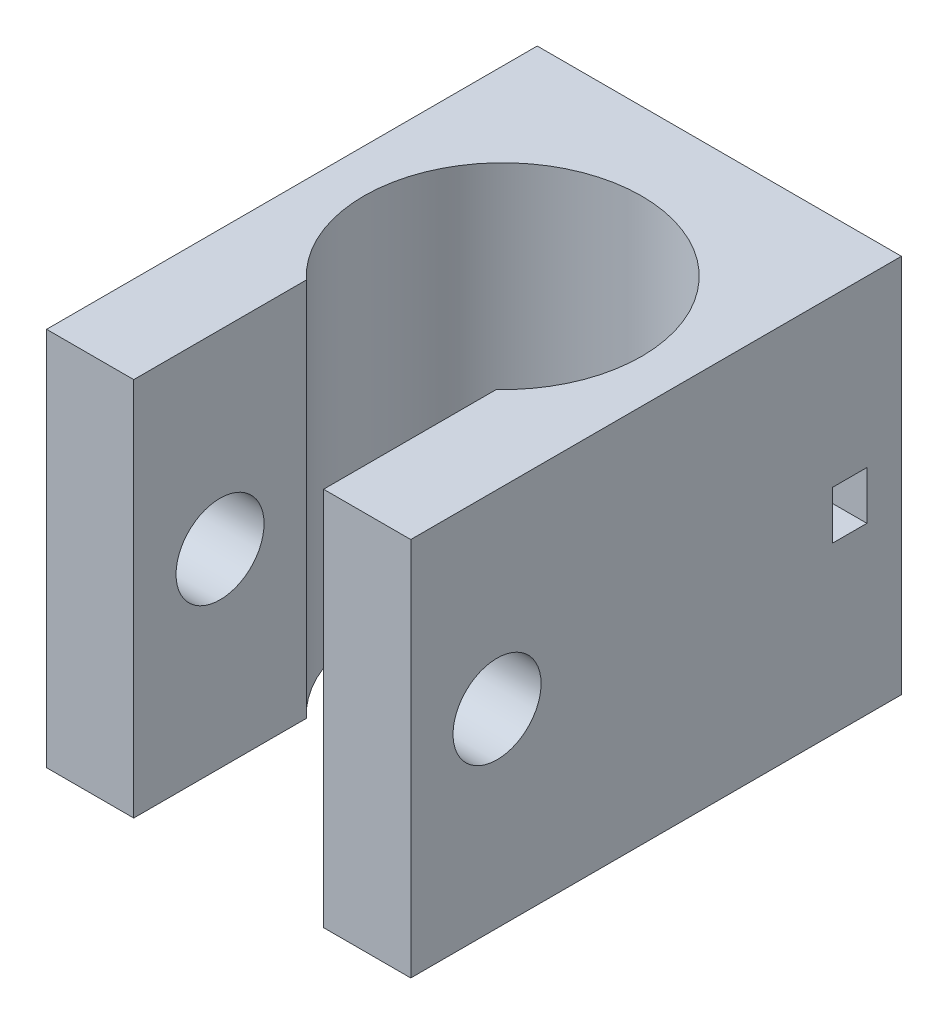
SolidWorks part; units mm, degrees
ref_plane "Front Plane" through (0, 0, 0) normal (0, 0, 1) x (1, 0, 0)
ref_plane "Top Plane" through (0, 0, 0) normal (0, 1, 0) x (1, 0, 0)
ref_plane "Right Plane" through (0, 0, 0) normal (1, 0, 0) x (0, 0, -1)
sketch "Sketch1" plane through (0, 0, 0) normal (0, 1, 0) x (1, 0, 0)
  line L0 (-5.5, -15) -> (-10.55, -15)
  line L1 (-10.55, -15) -> (-10.55, 13.4281)
  line L2 (-10.55, 13.4281) -> (10.55, 13.4281)
  line L3 (10.55, 13.4281) -> (10.55, -15)
  line L4 (10.55, -15) -> (5.5, -15)
  line L5 (5.5, -15) -> (5.5, -5)
  line L6 (-5.5, -15) -> (-5.5, -5)
  line L7 (-44.2539, 0) -> (44.2539, 0) construction
  line L8 (0, -44.7868) -> (0, 44.7868) construction
  arc A0 (-5.5, -5) -> (5.5, -5) centre (0, 0.8781) cw
  dimension "D1" = 8.05
  dimension "D2" = 11
  dimension "D3" = 10
  dimension "D4" = 10
  dimension "D5" = 21.1
  dimension "D6" = 12.55
  dimension "D7" = 15
  dimension "D8" = 10.55
extrude "Boss-Extrude1" add sketch "Sketch1" along normal mid plane 22
sketch "Sketch2" plane through (10.55, 0, 0) normal (1, 0, 0) x (0, 0, -1)
  line L0 (55, 0) -> (-55, 0) construction
  line L1 (-15, 11) -> (-15, -11) construction
  circle A0 centre (-10, 0) radius 2.55
  dimension "D1" = 5
  dimension "D2" = 5.1
extrude "Cut-Extrude1" cut sketch "Sketch2" against normal up to surface (21.1 mm away) up to face at (-10.55, 0, 0.7859)
sketch "Sketch4" plane through (10.55, 0, 0) normal (1, 0, 0) x (0, 0, -1)
  line L1 (9.4281, 1.4) -> (11.4281, 1.4)
  line L2 (9.4281, 1.4) -> (9.4281, -1.4)
  line L3 (9.4281, -1.4) -> (11.4281, -1.4)
  line L4 (11.4281, 1.4) -> (11.4281, -1.4)
  line L5 (-15, 11) -> (13.4281, 11) construction
  line L7 (13.4281, 11) -> (13.4281, -11) construction
  point P6 (10.4281, 1.4)
  dimension "D1" = 2
  dimension "D2" = 2.8
  dimension "D3" = 9.6
  dimension "D4" = 2
extrude "Cut-Extrude3" cut sketch "Sketch4" against normal up to surface (21.1 mm away) up to face at (-10.55, 0, 7.45)
sketch "Sketch5" plane through (0, 0, -13.4281) normal (0, 0, -1) x (-1, 0, 0)
  line L0 (10.55, 11) -> (10.55, -11) construction
  line L1 (-2.4, 8.55) -> (2.5, 8.55)
  line L2 (-2.4, 8.55) -> (-2.4, 3.65)
  line L3 (-2.4, 3.65) -> (2.5, 3.65)
  line L4 (2.5, 8.55) -> (2.5, 3.65)
  line L5 (2.5, -3.65) -> (-2.4, -3.65)
  line L6 (2.5, -3.65) -> (2.5, -8.55)
  line L7 (2.5, -8.55) -> (-2.4, -8.55)
  line L8 (-2.4, -3.65) -> (-2.4, -8.55)
  line L10 (-10.55, 11) -> (10.55, 11) construction
  line L11 (-10.55, -11) -> (10.55, -11) construction
  dimension "D1" = 4.9
  dimension "D5" = 8.05
  dimension "D6" = 8.05
  dimension "D7" = 2.45
  dimension "D8" = 2.45
extrude "Boss-Extrude2" add sketch "Sketch5" along normal blind 2
equation "\"Width\"=21.1"
equation "\"D5@Sketch1\"=\"Width\""
equation "\"D8@Sketch1\"=\"Width\"/2"
equation "\"D6@Sketch1\"=\"Width\"/2+2"
